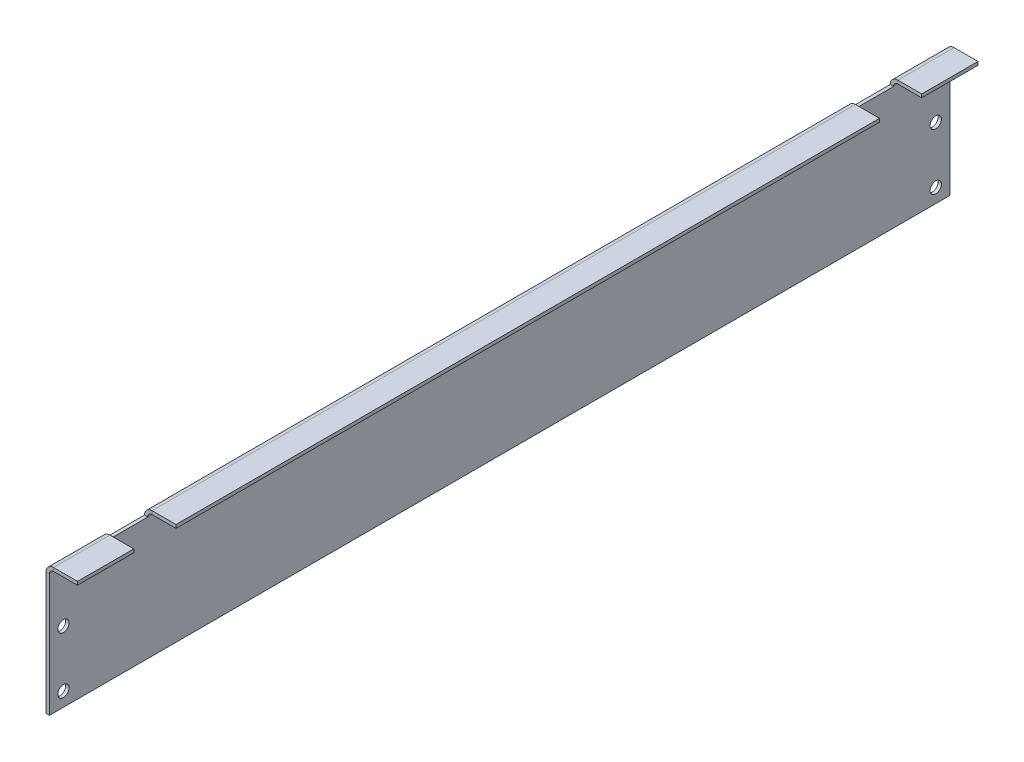
SolidWorks part; units mm, degrees
note: The reader was unsure of these and kept them because the rebuilt part matched: flange length of "Edge-Flange1".
ref_plane "Front Plane" through (0, 0, 0) normal (0, 0, 1) x (1, 0, 0)
ref_plane "Top Plane" through (0, 0, 0) normal (0, 1, 0) x (1, 0, 0)
ref_plane "Right Plane" through (0, 0, 0) normal (1, 0, 0) x (0, 0, -1)
sketch "Sketch1" plane through (0, 0, 0) normal (1, 0, 0) x (0, 0, -1)
  line L1 (-203.2, 29.3687) -> (203.2, 29.3687)
  line L2 (-203.2, 29.3687) -> (-203.2, -29.3687)
  line L3 (-203.2, -29.3687) -> (203.2, -29.3687)
  line L4 (203.2, 29.3687) -> (203.2, -29.3687)
  line L5 (-203.2, 29.3687) -> (203.2, -29.3687) construction
  line L6 (-203.2, -29.3687) -> (203.2, 29.3687) construction
  point P0 (0, 0)
  dimension "D1" = 406.4
  dimension "D2" = 58.7375
base flange "Base-Flange1" sketch "Sketch1" thickness 1.5189 reverse thickness direction no parameters "D1"=1.905
edge flange "Edge-Flange1" sketch "Sketch8" flange angle 90 flange length 12.7 flange position material inside bend radius 1.905 thickness 1.5189 relief rectangular parameters "D6"=10
sketch "Sketch8" plane through (0, 29.3687, 0) normal (0, 1, 0) x (0, 0, 1)
  line L2 (-203.2, 0) -> (-203.2, 12.7)
  line L3 (-203.2, 12.7) -> (203.2, 12.7)
  line L4 (203.2, 12.7) -> (203.2, 0)
  line L5 (-203.2, 0) -> (203.2, 0) construction
  line L6 (-203.2, 0) -> (203.2, 0)
bend "EdgeBend1" bend radius 1.905 bend angle 90 parameters "D5"=1
sketch "Sketch10" plane through (-1.5189, 0, 0) normal (-1, 0, 0) x (0, 0, 1)
  line L0 (203.2, 25.9448) -> (-203.2, 25.9448) construction
  line L1 (-177.8, 25.9448) -> (-158.75, 25.9448)
  line L2 (-177.8, 25.9448) -> (-177.8, 29.3688)
  line L3 (-177.8, 29.3688) -> (-158.75, 29.3688)
  line L4 (-158.75, 25.9448) -> (-158.75, 29.3688)
  line L5 (203.2, 29.3688) -> (-203.2, 29.3688) construction
  line L6 (-203.2, -29.3687) -> (-203.2, 25.9448) construction
  line L7 (158.75, 25.9448) -> (177.8, 25.9448)
  line L8 (158.75, 25.9448) -> (158.75, 29.3688)
  line L9 (158.75, 29.3688) -> (177.8, 29.3688)
  line L10 (177.8, 25.9448) -> (177.8, 29.3688)
  line L11 (203.2, 25.9448) -> (203.2, -29.3687) construction
  dimension "D1" = 19.05
  dimension "D2" = 25.4
  dimension "D3" = 25.4
extrude "Cut-Extrude2" cut sketch "Sketch10" against normal through all normal cut yes
hole_wizard "#10 Clearance Hole1" positions "Sketch12" profile "Sketch13" hole size "#10" standard "ANSI Inch" end condition up to next
sketch "Sketch12" plane through (0, 0, 0) normal (1, 0, 0) x (0, 0, -1)
  line L1 (-196.85, 2.3813) -> (196.85, 2.3813) construction
  line L2 (-196.85, 2.3813) -> (-196.85, -23.0187) construction
  line L3 (-196.85, -23.0187) -> (196.85, -23.0187) construction
  line L4 (196.85, 2.3813) -> (196.85, -23.0187) construction
  line L5 (-203.2, -29.3687) -> (203.2, -29.3687) construction
  line L6 (-203.2, 25.9448) -> (-203.2, -29.3687) construction
  point P1 (-196.85, 2.3813)
  point P2 (196.85, -23.0187)
  point P103 (-196.85, -23.0187)
  point P104 (196.85, 2.3813)
  dimension "D1" = 393.7
  dimension "D2" = 25.4
  dimension "D3" = 6.35
  dimension "D4" = 6.35
sketch "Sketch13" plane through (0, 2.3813, 196.85) normal (0, 1, 0) x (0, 0, -1)
  line L0 (0, 0) -> (0, 1.5189)
  line L1 (0, 1.5189) -> (2.5527, 1.5189)
  line L2 (2.5527, 1.5189) -> (2.5527, 0)
  line L5 (2.5527, 0) -> (0, 0)
  line L11 (0, -6.35) -> (0, 107.95) construction
  dimension "Thru Hole Dia." = 5.1054
  dimension "Thru Hole Depth" = 1.5189
sketch "Bend-Lines1" [suppressed] plane through (0, 0, 0) normal (0, 1, 0) x (1, 0, 0)
sketch "Bounding-Box1" [suppressed] plane through (0, 0, 0) normal (0, 1, 0) x (1, 0, 0)
sheet metal parameters "Sheet-Metal(1)" thickness 1.5189 parameters "D1"=1.905
flat pattern "Flat-Pattern(1)" [suppressed]
sketch "Bend-Lines2" plane through (0, 0, 0) normal (0, 1, 0) x (1, 0, 0)
sketch "Bounding-Box2" [suppressed] plane through (0, 0, 0) normal (0, 1, 0) x (1, 0, 0)
sheet metal parameters "Sheet-Metal(2)" thickness 1.5189 parameters "D1"=1.905
flat pattern "Flat-Pattern(1)"
sketch "Bend-Lines2" plane through (0, 0, 0) normal (1, 0, 0) x (0, 0, -1)
  line L0 (202.9598, 28.8312) -> (-203.2, 28.8312) construction
  line L1 (202.9598, 28.8312) -> (-203.2, 28.8312) construction
sketch3d "Bounding-Box2" [suppressed]
  line L0 (-203.2, -30.1625, 0) -> (203.2, -30.1625, 0) construction
  line L1 (-203.2, 41.7189, 0) -> (203.2, 41.7189, 0) construction
  line L2 (-203.2, -30.1625, 0) -> (-203.2, 41.7189, 0) construction
  line L3 (203.2, -30.1625, 0) -> (203.2, 41.7189, 0) construction
bend of the flat pattern "Flatten-<EdgeBend1>1"
sheet metal parameters "Sheet-Metal(4)" thickness 1.5189 parameters "D1"=1.905
flat pattern "Flat-Pattern(1)"
sketch "Bend-Lines2" plane through (0, 0, 0) normal (1, 0, 0) x (0, 0, -1)
  line L0 (203.2, 28.8312) -> (177.8, 28.8312) construction
  line L1 (203.2, 28.8312) -> (177.8, 28.8312) construction
  line L2 (-177.8, 28.8312) -> (-203.2, 28.8312) construction
  line L3 (158.75, 28.8312) -> (-158.75, 28.8312) construction
sketch3d "Bounding-Box2" [suppressed]
  line L0 (-203.2, -30.1625, 0) -> (203.2, -30.1625, 0) construction
  line L1 (-203.2, 41.7189, 0) -> (203.2, 41.7189, 0) construction
  line L2 (-203.2, -30.1625, 0) -> (-203.2, 41.7189, 0) construction
  line L3 (203.2, -30.1625, 0) -> (203.2, 41.7189, 0) construction
bend of the flat pattern "Flatten-<EdgeBend1>1"
sheet metal parameters "Sheet-Metal(5)" thickness 1.5189 parameters "D1"=1.905
flat pattern "Flat-Pattern(1)"
sketch "Bend-Lines2" plane through (0, 0, 0) normal (1, 0, 0) x (0, 0, -1)
  line L0 (203.2, 28.8312) -> (177.8, 28.8312) construction
  line L1 (203.2, 28.8312) -> (177.8, 28.8312) construction
  line L2 (-177.8, 28.8312) -> (-203.2, 28.8312) construction
  line L3 (158.75, 28.8312) -> (-158.75, 28.8312) construction
sketch3d "Bounding-Box2" [suppressed]
  line L0 (-203.2, -30.1625, 0) -> (203.2, -30.1625, 0) construction
  line L1 (-203.2, 41.7189, 0) -> (203.2, 41.7189, 0) construction
  line L2 (-203.2, -30.1625, 0) -> (-203.2, 41.7189, 0) construction
  line L3 (203.2, -30.1625, 0) -> (203.2, 41.7189, 0) construction
bend of the flat pattern "Flatten-<EdgeBend1>1"
